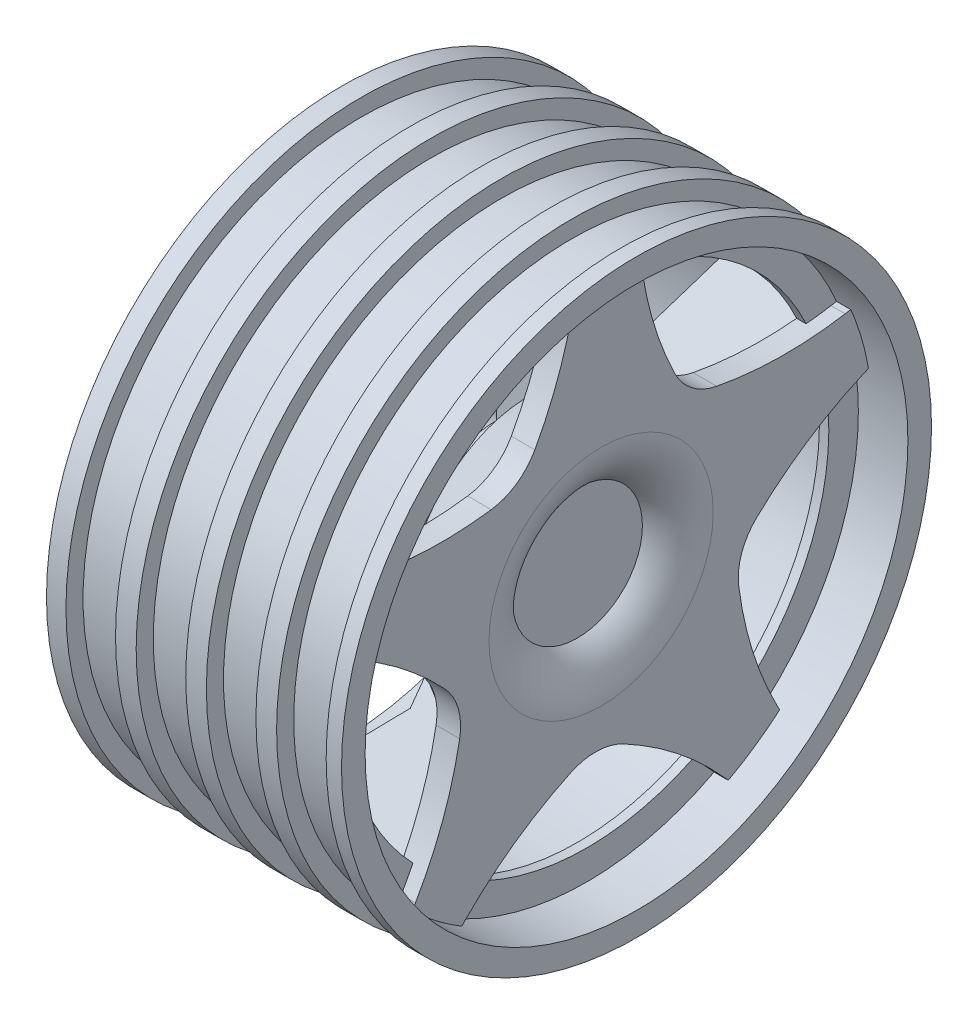
SolidWorks part; units mm, degrees
ref_plane "Alzado" through (0, 0, 0) normal (0, 0, 1) x (1, 0, 0)
ref_plane "Planta" through (0, 0, 0) normal (0, 1, 0) x (1, 0, 0)
ref_plane "Vista lateral" through (0, 0, 0) normal (1, 0, 0) x (0, 0, -1)
sketch "Croquis1" plane through (0, 0, 0) normal (1, 0, 0) x (0, 0, -1)
  circle A0 centre (0, 0) radius 25
  dimension "D1" = 50
extrude "Saliente-Extruir1" add sketch "Croquis1" along normal blind 30
sketch "Croquis2" plane through (0, 0, 0) normal (-1, 0, 0) x (0, 0, 1)
  line L1 (-2.2361, -2) -> (2.2361, -2)
  line L3 (-2.2361, 2) -> (2.2361, 2)
  circle A0 centre (0, 0) radius 5.5
  circle A1 centre (0, 0) radius 32.5
  arc A2 (-2.2361, 2) -> (-2.2361, -2) centre (0, 0) ccw
  arc A3 (2.2361, -2) -> (2.2361, 2) centre (0, 0) ccw
  circle A4 centre (0, 0) radius 23
  circle M1 centre (0, 0) radius 25
extrude "Cortar-Extruir1" cut sketch "Croquis2" against normal blind 5 contours A0 M1 | A4 A0 region at (0, 0, -22.3495) region at (0, 0, -24.2929)
extrude "Cortar-Extruir2" cut sketch "Croquis2<3>" against normal blind 14 contours L1 A3 L3 A2 region at (0, 0, 0)
sketch "Croquis2<3>" plane through (0, 0, 0) normal (-1, 0, 0) x (0, 0, 1) same geometry as "Croquis2"
extrude "Cortar-Extruir3" cut sketch "Croquis2<4>" against normal blind 25 contours A4 A0 region at (0, 0, -22.3495)
sketch "Croquis2<4>" plane through (0, 0, 0) normal (-1, 0, 0) x (0, 0, 1) same geometry as "Croquis2"
sketch "Croquis4" plane through (30, 0, 0) normal (1, 0, 0) x (0, 0, -1)
  circle A0 centre (0, 0) radius 23
extrude "Cortar-Extruir4" cut sketch "Croquis4" against normal blind 4.2
sketch "Croquis5" plane through (25.8, 0, 0) normal (1, 0, 0) x (0, 0, -1)
  circle A0 centre (0, 0) radius 20.5
  circle A1 centre (0, 0) radius 5.5
  circle A2 centre (0, 0) radius 5.5 construction
extrude "Cortar-Extruir5" cut sketch "Croquis5" against normal up to surface (0.8 mm away) contours A0 up to face at (25, 0, 5.5)
ref_plane "Plano1" through (28.7, 0, 0) normal (1, 0, 0) x (0, 0, -1)
sketch "Croquis6" plane through (28.7, 0, 0) normal (1, 0, 0) x (0, 0, -1)
  circle A0 centre (0, 0) radius 23.55
extrude "Cortar-Extruir7" cut sketch "Croquis6" against normal blind 4.2 flip side to cut
ref_plane "Plano2" through (18.55, 0, 0) normal (1, 0, 0) x (0, 0, -1)
ref_plane "Plano3" through (12.6, 0, 0) normal (1, 0, 0) x (0, 0, -1)
ref_plane "Plano4" through (6.65, 0, 0) normal (1, 0, 0) x (0, 0, -1)
sketch "Croquis7" plane through (6.65, 0, 0) normal (1, 0, 0) x (0, 0, -1)
  circle A0 centre (0, 0) radius 23.55
  circle A1 centre (0, 0) radius 23.55 construction
extrude "Cortar-Extruir8" cut sketch "Croquis7" along normal blind 4.2 flip side to cut
sketch "Croquis8" plane through (12.6, 0, 0) normal (1, 0, 0) x (0, 0, -1)
  circle A0 centre (0, 0) radius 23.55
  circle A1 centre (0, 0) radius 23.55 construction
extrude "Cortar-Extruir9" cut sketch "Croquis8" along normal blind 4.2 flip side to cut
sketch "Croquis9" plane through (18.55, 0, 0) normal (1, 0, 0) x (0, 0, -1)
  circle A0 centre (0, 0) radius 23.55
  circle A1 centre (0, 0) radius 23.55 construction
extrude "Cortar-Extruir10" cut sketch "Croquis9" along normal blind 4.2 flip side to cut
sketch "Croquis10" plane through (25, 0, 0) normal (1, 0, 0) x (0, 0, -1)
  line L10 (-2.0392, 22.9925) -> (3.2108, 22.9925)
  line L11 (-2.0392, 22.9925) -> (-3.87, 10.8293)
  line L12 (3.2108, 22.9925) -> (4.444, 10.6067)
  circle A1 centre (0, 0) radius 11.5
  circle M2 centre (0, 0) radius 5.5
  dimension "D1" = 5.25
extrude "Saliente-Extruir2" add sketch "Croquis10" along normal blind 2 contours A1 L12 L10 L11 region at (25, 16.6875, -0.4406)
pattern_circular "MatrizC1" count 5 over 360 about axis through (25, 0, 0) along (1, 0, 0) of "Saliente-Extruir2"
extrude "Saliente-Extruir3" add sketch "Croquis10<3>" along normal blind 2 contours A1 M2 region at (25, 11.1707, -0.2991)
sketch "Croquis10<3>" plane through (25, 0, 0) normal (1, 0, 0) x (0, 0, -1) same geometry as "Croquis10"
fillet "Redondeo1" radius 31 10 edges at (26, 7.5041, 8.7143) (26, 10.8293, 3.87) (26, -5.9689, 9.8297) (26, -0.3342, 11.4951) (26, -11.0358, 3.2344) (26, -11.1931, -2.6392) (26, -6.4863, -9.4962) (26, -0.9488, -11.4608) (26, 7.027, -9.1034) (26, 10.6067, -4.444)
fillet "Redondeo2" radius 5 6 edges at (27, 0, -5.5) (26, 10.009, 6.8836) (26, -3.4538, 11.6463) (26, -12.1435, 0.3141) (26, -4.0513, -11.4521) (26, 9.6397, -7.3919)
sketch "Croquis11" plane through (25, 0, 0) normal (-1, 0, 0) x (0, 0, 1)
  line L2 (-0.5, 12.624) -> (-0.5, 7.1074)
  line L3 (-0.5, 7.1074) -> (0.5, 7.1074)
  line L4 (0.5, 12.624) -> (0.5, 7.1074)
  line L6 (0.5, -23) -> (-0.5, -23)
  line L7 (0.5, 23) -> (-0.5, 23)
  line L10 (0.5, 23) -> (0.4922, 22.6424) construction
  line L11 (0.5, 12.624) -> (0.5, 23)
  line L12 (-0.4922, 22.6424) -> (-0.5, 23) construction
  line L13 (-0.5, 12.624) -> (-0.5, 23)
  circle A1 centre (0, 0) radius 12.6339
  circle A2 centre (0, 0) radius 7.125
extrude "Saliente-Extruir4" add sketch "Croquis11" along normal blind 4 draft 30 contours A1
extrude "Saliente-Extruir5" add sketch "Croquis11<3>" along normal blind 7.35 contours A2
sketch "Croquis11<3>" plane through (25, 0, 0) normal (-1, 0, 0) x (0, 0, 1) same geometry as "Croquis11"
fillet "Redondeo3" radius 1 1 edges at (17.65, 0, 7.125)
extrude "Saliente-Extruir6" add sketch "Croquis11<5>" along normal blind 9 contours L11 L7 L13 L2 L3 L4
sketch "Croquis11<5>" plane through (25, 0, 0) normal (-1, 0, 0) x (0, 0, 1) same geometry as "Croquis11"
pattern_circular "MatrizC2" count 5 over 360 about axis through (0, 0, 0) along (-1, 0, 0) of "Saliente-Extruir6"
sketch "Croquis12" plane through (0, -0.4755, 0.1545) normal (0, -0.9511, 0.309) x (1, 0, 0)
  line L0 (18.65, 7.1074) -> (18.65, 12.624)
  line L1 (25, 12.624) -> (18.65, 12.624) construction
  line L2 (16, 22.9946) -> (16, 15.9946) construction
  line L3 (16, 22.9946) -> (16, 7.1074) construction
  line L4 (18.65, 12.624) -> (16, 15.9946)
  line L5 (0, 0) -> (30.6352, 0) construction
  line L6 (16, 15.9946) -> (16, 7.1074)
  line L7 (16, 7.1074) -> (18.65, 7.1074)
  line L9 (0, 5.5) -> (0, -5.5) construction
extrude "Cortar-Extruir11" cut sketch "Croquis12" against normal blind 1
pattern_circular "MatrizC3" count 5 over 360 about axis through (17.65, 0, 0) along (-1, 0, 0) of "Cortar-Extruir11"
